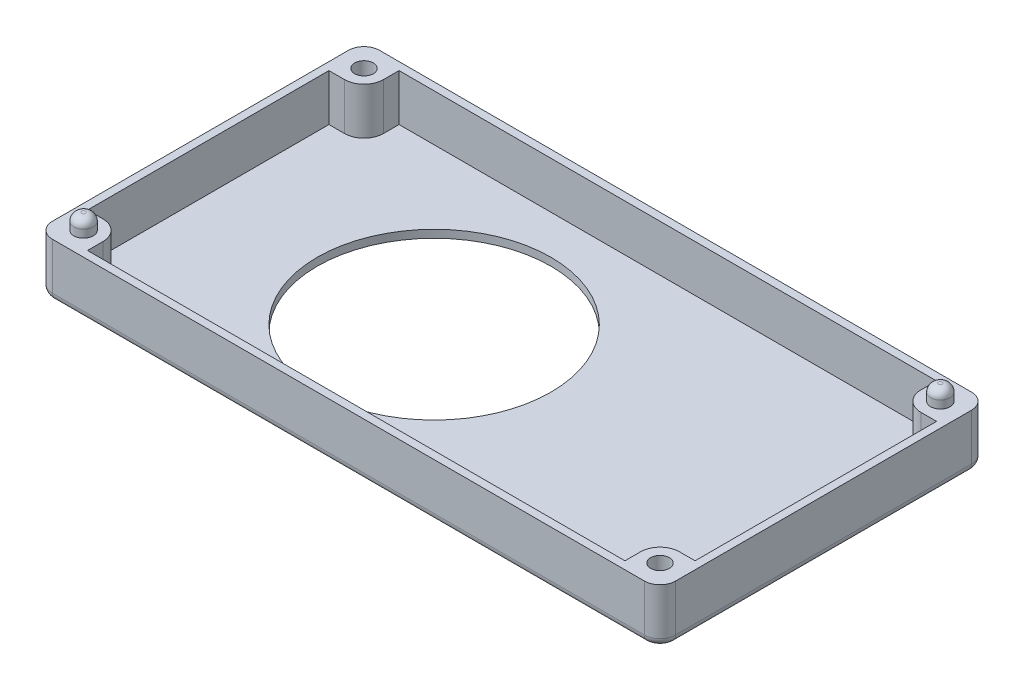
SolidWorks part; units mm, degrees
ref_plane "Front Plane" through (0, 0, 0) normal (0, 0, 1) x (1, 0, 0)
ref_plane "Top Plane" through (0, 0, 0) normal (0, 1, 0) x (1, 0, 0)
ref_plane "Right Plane" through (0, 0, 0) normal (1, 0, 0) x (0, 0, -1)
sketch "Sketch1" plane through (0, 0, 0) normal (0, 1, 0) x (1, 0, 0)
  line L1 (-40, -21) -> (40, -21)
  line L2 (-40, -21) -> (-40, 21)
  line L3 (-40, 21) -> (40, 21)
  line L4 (40, -21) -> (40, 21)
  line L5 (-40, -21) -> (40, 21) construction
  line L6 (-40, 21) -> (40, -21) construction
  point P0 (0, 0)
  dimension "D1" = 42
  dimension "D2" = 80
extrude "Boss-Extrude1" add sketch "Sketch1" along normal blind 7
sketch "Sketch2" plane through (0, 7, 0) normal (0, 1, 0) x (1, 0, 0)
  line L0 (40, -21) -> (40, 21) construction
  line L1 (-39, -20) -> (39, -20)
  line L2 (-39, -20) -> (-39, 20)
  line L3 (-39, 20) -> (39, 20)
  line L4 (39, -20) -> (39, 20)
  line L5 (-39, -20) -> (39, 20) construction
  line L6 (-39, 20) -> (39, -20) construction
  line L7 (40, 21) -> (-40, 21) construction
  point P0 (0, 0)
  dimension "D1" = 1
  dimension "D2" = 1
extrude "Cut-Extrude1" cut sketch "Sketch2" against normal offset from surface (6 mm away) 1 up to face at (0, 0, 0)
fillet "Fillet1" radius 2 8 edges at (40, 3.5, -21) (40, 3.5, 21) (-40, 3.5, 21) (-40, 3.5, -21) (39, 4, 20) (-39, 4, 20) (39, 4, -20) (-39, 4, -20)
sketch "Sketch3" plane through (0, 7, 0) normal (0, 1, 0) x (1, 0, 0)
  line L0 (-34.5, 18) -> (-34.5, 20)
  line L1 (37, 20) -> (-37, 20) construction
  line L2 (-37, 15.5) -> (-39, 15.5)
  line L3 (-39, 18) -> (-39, -18) construction
  line L4 (-39, 18) -> (-39, -18) construction
  line L5 (-39, 18) -> (-39, 15.5)
  line L6 (-34.5, 20) -> (-37, 20)
  arc A0 (-37, 15.5) -> (-34.5, 18) centre (-37, 18) ccw
  arc A1 (-37, 20) -> (-39, 18) centre (-37, 18) ccw construction
  arc A2 (-37, 20) -> (-39, 18) centre (-37, 18) ccw
  dimension "D1" = 5
extrude "Boss-Extrude2" add sketch "Sketch3" against normal up to next
mirror "Mirror1" about plane through (0, 0, 0) normal (0, 0, 1) of "Boss-Extrude2" second plane through (0, 0, 0) second plane normal (1, 0, 0)
hole_wizard "M2 Clearance Hole2" positions "3DSketch2" profile "Sketch8" hole size "M2" standard "ANSI Metric" end condition through all
sketch3d "3DSketch2"
  line L0 (-37, 1, -18) -> (-37, 7, -18) construction
  line L2 (37, 1, 18) -> (37, 7, 18) construction
  point P0 (-37, 7, -18)
  point P10 (37, 7, 18)
sketch "Sketch8" plane through (-37, 7, -18) normal (1, 0, 0) x (0, 0, 1)
  line L0 (0, 0) -> (0, 7)
  line L1 (0, 7) -> (1.2, 7)
  line L2 (1.2, 7) -> (1.2, 0)
  line L5 (1.2, 0) -> (0, 0)
  line L11 (0, -6.35) -> (0, 107.95) construction
  dimension "Thru Hole Dia." = 2.4
  dimension "Thru Hole Depth" = 7
sketch "Sketch9" plane through (0, 0, 0) normal (0, -1, 0) x (1, 0, 0)
  circle A0 centre (-37, -18) radius 2
  circle A1 centre (37, 18) radius 2
  dimension "D1" = 4
extrude "Cut-Extrude2" cut sketch "Sketch9" against normal blind 2.5
sketch "Sketch11" plane through (0, 7, 0) normal (0, 1, 0) x (1, 0, 0)
  circle A0 centre (-37, -18) radius 1.25
  circle A1 centre (37, 18) radius 1.25
  dimension "D1" = 2.5
extrude "Boss-Extrude3" add sketch "Sketch11" along normal blind 2
fillet "Fillet2" radius 1 2 edges at (37, 9, -16.75) (-37, 9, 19.25)
fillet "Fillet3" radius 1 8 edges at (-39.4142, 0, -20.4142) (0, 0, -21) (39.4142, 0, -20.4142) (40, 0, 0) (39.4142, 0, 20.4142) (0, 0, 21) (-39.4142, 0, 20.4142) (-40, 0, 0)
sketch "Sketch12" plane through (0, 0, 0) normal (0, -1, 0) x (1, 0, 0)
  line L0 (55, 0) -> (-55, 0) construction
  line L1 (-40, -19) -> (-40, 19) construction
  circle A0 centre (-10, 0) radius 15
  dimension "D1" = 30
  dimension "D2" = 30
extrude "Cut-Extrude3" cut sketch "Sketch12" against normal up to next
